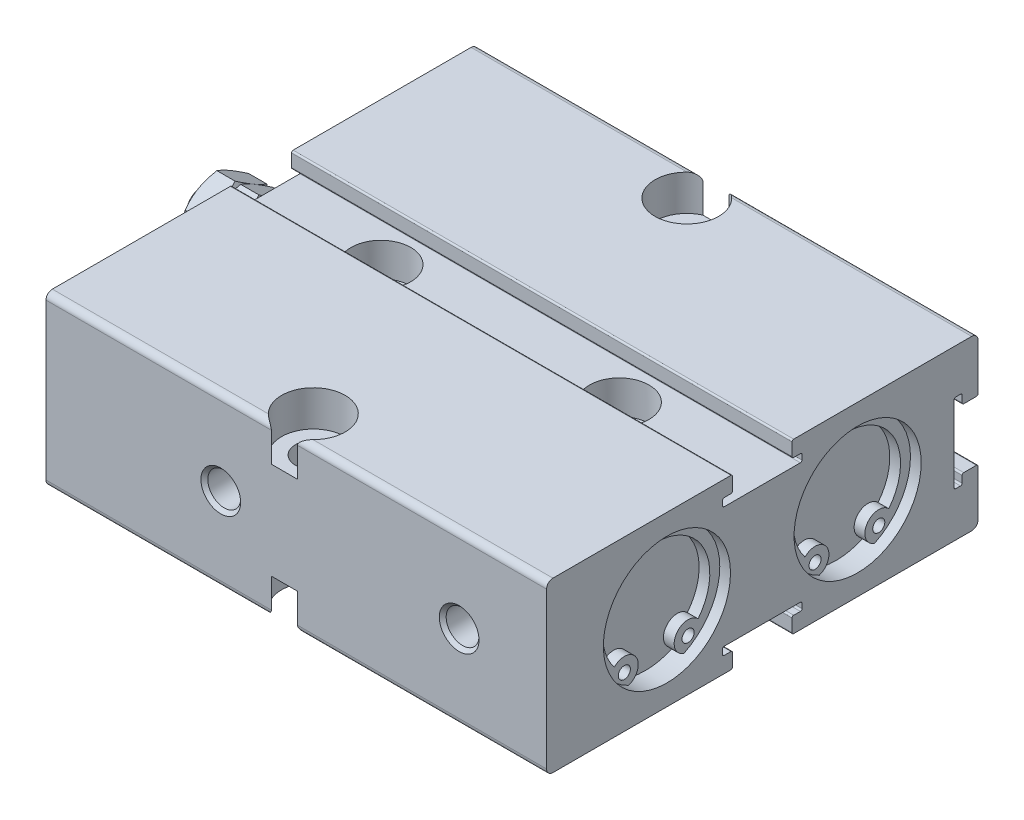
SolidWorks part; units mm, degrees
ref_plane "前视基准面" through (0, 0, 0) normal (0, 0, 1) x (1, 0, 0)
ref_plane "上视基准面" through (0, 0, 0) normal (0, 1, 0) x (1, 0, 0)
ref_plane "右视基准面" through (0, 0, 0) normal (1, 0, 0) x (0, 0, -1)
sketch "草图1" plane through (0, 0, 0) normal (1, 0, 0) x (0, 0, -1)
  line L0 (-26.35, 0) -> (-3.95, 0)
  line L1 (-3.75, 0.2) -> (-3.75, 1.8)
  line L2 (-3.95, 2) -> (-4.8, 2)
  line L3 (-5, 2.2) -> (-5, 2.8)
  line L4 (-4.8, 3) -> (4.8, 3)
  line L5 (5, 2.8) -> (5, 2.2)
  line L6 (4.8, 2) -> (3.95, 2)
  line L7 (3.75, 1.8) -> (3.75, 0.2)
  line L8 (3.95, 0) -> (26.35, 0)
  line L9 (27.15, 0.8) -> (27.15, 6.65)
  line L10 (26.95, 6.85) -> (25.35, 6.85)
  line L11 (25.15, 6.65) -> (25.15, 5.8)
  line L12 (24.95, 5.6) -> (24.35, 5.6)
  line L13 (24.15, 5.8) -> (24.15, 15.4)
  line L14 (24.35, 15.6) -> (24.95, 15.6)
  line L15 (25.15, 15.4) -> (25.15, 14.55)
  line L16 (25.35, 14.35) -> (26.95, 14.35)
  line L17 (27.15, 14.55) -> (27.15, 20.4)
  line L18 (26.35, 21.2) -> (3.95, 21.2)
  line L19 (3.75, 21) -> (3.75, 19.4)
  line L20 (3.95, 19.2) -> (4.8, 19.2)
  line L21 (5, 19) -> (5, 18.4)
  line L22 (4.8, 18.2) -> (-4.8, 18.2)
  line L23 (-5, 18.4) -> (-5, 19)
  line L24 (-4.8, 19.2) -> (-3.95, 19.2)
  line L25 (-3.75, 19.4) -> (-3.75, 21)
  line L26 (-3.95, 21.2) -> (-26.35, 21.2)
  line L27 (-27.15, 20.4) -> (-27.15, 0.8)
  arc A0 (-27.15, 0.8) -> (-26.35, 0) centre (-26.35, 0.8) ccw
  arc A1 (-3.95, 0) -> (-3.75, 0.2) centre (-3.95, 0.2) ccw
  arc A2 (-3.75, 1.8) -> (-3.95, 2) centre (-3.95, 1.8) ccw
  arc A3 (-4.8, 2) -> (-5, 2.2) centre (-4.8, 2.2) cw
  arc A4 (-5, 2.8) -> (-4.8, 3) centre (-4.8, 2.8) cw
  arc A5 (4.8, 3) -> (5, 2.8) centre (4.8, 2.8) cw
  arc A6 (5, 2.2) -> (4.8, 2) centre (4.8, 2.2) cw
  arc A7 (3.95, 2) -> (3.75, 1.8) centre (3.95, 1.8) ccw
  arc A8 (3.75, 0.2) -> (3.95, 0) centre (3.95, 0.2) ccw
  arc A9 (26.35, 0) -> (27.15, 0.8) centre (26.35, 0.8) ccw
  arc A10 (27.15, 6.65) -> (26.95, 6.85) centre (26.95, 6.65) ccw
  arc A11 (25.35, 6.85) -> (25.15, 6.65) centre (25.35, 6.65) ccw
  arc A12 (25.15, 5.8) -> (24.95, 5.6) centre (24.95, 5.8) cw
  arc A13 (24.35, 5.6) -> (24.15, 5.8) centre (24.35, 5.8) cw
  arc A14 (24.15, 15.4) -> (24.35, 15.6) centre (24.35, 15.4) cw
  arc A15 (24.95, 15.6) -> (25.15, 15.4) centre (24.95, 15.4) cw
  arc A16 (25.15, 14.55) -> (25.35, 14.35) centre (25.35, 14.55) ccw
  arc A17 (26.95, 14.35) -> (27.15, 14.55) centre (26.95, 14.55) ccw
  arc A18 (27.15, 20.4) -> (26.35, 21.2) centre (26.35, 20.4) ccw
  arc A19 (3.95, 21.2) -> (3.75, 21) centre (3.95, 21) ccw
  arc A20 (3.75, 19.4) -> (3.95, 19.2) centre (3.95, 19.4) ccw
  arc A21 (4.8, 19.2) -> (5, 19) centre (4.8, 19) cw
  arc A22 (5, 18.4) -> (4.8, 18.2) centre (4.8, 18.4) cw
  arc A23 (-4.8, 18.2) -> (-5, 18.4) centre (-4.8, 18.4) cw
  arc A24 (-5, 19) -> (-4.8, 19.2) centre (-4.8, 19) cw
  arc A25 (-3.95, 19.2) -> (-3.75, 19.4) centre (-3.95, 19.4) ccw
  arc A26 (-3.75, 21) -> (-3.95, 21.2) centre (-3.95, 21) ccw
  arc A27 (-26.35, 21.2) -> (-27.15, 20.4) centre (-26.35, 20.4) ccw
extrude "凸台-拉伸1" add sketch "草图1" along normal blind 63
ref_plane "基准面1" through (0, 0, 12) normal (0, 0, 1) x (1, 0, 0)
sketch "草图2" plane through (0, 0, 12) normal (0, 0, 1) x (1, 0, 0)
  line L0 (0, 10.6) -> (0, 14.6)
  line L1 (0, 14.6) -> (33.4, 14.6)
  line L2 (33.4, 14.6) -> (33.4, 18.6)
  line L3 (33.4, 18.6) -> (57.6, 18.6)
  line L4 (57.6, 18.6) -> (57.6, 10.6)
  line L5 (57.6, 10.6) -> (0, 10.6)
  line L6 (57.6, 10.6) -> (0, 10.6) construction
revolve "切除-旋转1" cut sketch "草图2" angle 360 about L6 reverse direction yes
ref_plane "基准面2" through (0, 0, -12) normal (0, 0, 1) x (1, 0, 0)
sketch "草图3" plane through (0, 0, -12) normal (0, 0, 1) x (1, 0, 0)
  line L0 (0, 10.6) -> (0, 14.6)
  line L1 (0, 14.6) -> (33.4, 14.6)
  line L2 (33.4, 14.6) -> (33.4, 18.6)
  line L3 (33.4, 18.6) -> (57.6, 18.6)
  line L4 (57.6, 18.6) -> (57.6, 10.6)
  line L5 (57.6, 10.6) -> (0, 10.6)
  line L6 (57.6, 10.6) -> (0, 10.6) construction
revolve "切除-旋转2" cut sketch "草图3" angle 360 about L6 reverse direction yes
sketch "草图4" plane through (0, 0, 0) normal (0, 0, 1) x (1, 0, 0)
  line L0 (15, 21.2) -> (18.75, 21.2)
  line L1 (18.75, 21.2) -> (18.75, 14)
  line L2 (18.75, 14) -> (17.25, 14)
  line L3 (17.25, 14) -> (17.25, 7.2)
  line L4 (17.25, 7.2) -> (18.75, 7.2)
  line L5 (18.75, 7.2) -> (18.75, 0)
  line L6 (18.75, 0) -> (15, 0)
  line L7 (15, 0) -> (15, 21.2)
  line L8 (15, 0) -> (15, 21.2) construction
revolve "切除-旋转3" cut sketch "草图4" angle 360 about L8 reverse direction yes
sketch "草图5" plane through (0, 0, 0) normal (0, 0, 1) x (1, 0, 0)
  line L0 (45, 21.2) -> (48.75, 21.2)
  line L1 (48.75, 21.2) -> (48.75, 14)
  line L2 (48.75, 14) -> (47.25, 14)
  line L3 (47.25, 14) -> (47.25, 7.2)
  line L4 (47.25, 7.2) -> (48.75, 7.2)
  line L5 (48.75, 7.2) -> (48.75, 0)
  line L6 (48.75, 0) -> (45, 0)
  line L7 (45, 0) -> (45, 21.2)
  line L8 (45, 0) -> (45, 21.2) construction
revolve "切除-旋转4" cut sketch "草图5" angle 360 about L8 reverse direction yes
ref_plane "基准面3" through (0, 0, 23.5) normal (0, 0, 1) x (1, 0, 0)
sketch "草图6" plane through (0, 0, 23.5) normal (0, 0, 1) x (1, 0, 0)
  line L0 (30, 21.2) -> (34, 21.2)
  line L1 (34, 21.2) -> (34, 16.7)
  line L2 (34, 16.7) -> (32.25, 16.7)
  line L3 (32.25, 16.7) -> (32.25, 4.5)
  line L4 (32.25, 4.5) -> (34, 4.5)
  line L5 (34, 4.5) -> (34, 0)
  line L6 (34, 0) -> (30, 0)
  line L7 (30, 0) -> (30, 21.2)
  line L8 (30, 0) -> (30, 21.2) construction
revolve "切除-旋转5" cut sketch "草图6" angle 360 about L8 reverse direction yes
ref_plane "基准面4" through (0, 0, -23.5) normal (0, 0, 1) x (1, 0, 0)
sketch "草图7" plane through (0, 0, -23.5) normal (0, 0, 1) x (1, 0, 0)
  line L0 (30, 21.2) -> (34, 21.2)
  line L1 (34, 21.2) -> (34, 16.7)
  line L2 (34, 16.7) -> (32.25, 16.7)
  line L3 (32.25, 16.7) -> (32.25, 4.5)
  line L4 (32.25, 4.5) -> (34, 4.5)
  line L5 (34, 4.5) -> (34, 0)
  line L6 (34, 0) -> (30, 0)
  line L7 (30, 0) -> (30, 21.2)
  line L8 (30, 0) -> (30, 21.2) construction
revolve "切除-旋转6" cut sketch "草图7" angle 360 about L8 reverse direction yes
ref_plane "基准面5" through (63, 0, 0) normal (1, 0, 0) x (0, 0, -1)
sketch "草图8" plane through (63, 0, 0) normal (1, 0, 0) x (0, 0, -1)
  circle A0 centre (12, 10.6) radius 8
extrude "切除-拉伸1" cut sketch "草图8" against normal blind 2.7
sketch "草图9" plane through (63, 0, 0) normal (1, 0, 0) x (0, 0, -1)
  circle A0 centre (-12, 10.6) radius 8
extrude "切除-拉伸2" cut sketch "草图9" against normal blind 2.7
sketch "草图10" plane through (0, 0, 0) normal (1, 0, 0) x (0, 0, -1)
  circle A0 centre (12, 10.6) radius 8
extrude "切除-拉伸3" cut sketch "草图10" along normal blind 2.7
sketch "草图11" plane through (0, 0, 0) normal (1, 0, 0) x (0, 0, -1)
  circle A0 centre (-12, 10.6) radius 8
extrude "切除-拉伸4" cut sketch "草图11" along normal blind 2.7
ref_plane "基准面6" through (22, 0, 0) normal (1, 0, 0) x (0, 0, -1)
sketch "草图12" plane through (22, 0, 0) normal (1, 0, 0) x (0, 0, -1)
  line L0 (-27.15, 10.6) -> (-27.15, 13.1)
  line L1 (-27.15, 13.1) -> (-26.717, 12.667)
  line L2 (-26.717, 12.667) -> (-22.15, 12.667)
  line L3 (-22.15, 12.667) -> (-22.15, 10.6)
  line L4 (-22.15, 10.6) -> (-27.15, 10.6)
  line L5 (-22.15, 10.6) -> (-27.15, 10.6) construction
revolve "切除-旋转7" cut sketch "草图12" angle 360 about L5 reverse direction yes
cosmetic thread "装饰螺纹线1" parameters "D1"=5, "D2"=5
ref_plane "基准面7" through (52, 0, 0) normal (1, 0, 0) x (0, 0, -1)
sketch "草图13" plane through (52, 0, 0) normal (1, 0, 0) x (0, 0, -1)
  line L0 (-27.15, 10.6) -> (-27.15, 13.1)
  line L1 (-27.15, 13.1) -> (-26.717, 12.667)
  line L2 (-26.717, 12.667) -> (-22.15, 12.667)
  line L3 (-22.15, 12.667) -> (-22.15, 10.6)
  line L4 (-22.15, 10.6) -> (-27.15, 10.6)
  line L5 (-22.15, 10.6) -> (-27.15, 10.6) construction
revolve "切除-旋转8" cut sketch "草图13" angle 360 about L5 reverse direction yes
cosmetic thread "装饰螺纹线2" parameters "D1"=5, "D2"=5
sketch "草图14" plane through (0, 0, 0) normal (0, 0, 1) x (1, 0, 0)
  line L0 (-6, 13.5) -> (-6, 17.5)
  line L1 (-6, 17.5) -> (-5.5381, 18.3)
  line L2 (-5.5381, 18.3) -> (-3.4619, 18.3)
  line L3 (-3.4619, 18.3) -> (-3, 17.5)
  line L4 (-3, 17.5) -> (-2.5381, 18.3)
  line L5 (-2.5381, 18.3) -> (-0.4619, 18.3)
  line L6 (-0.4619, 18.3) -> (0, 17.5)
  line L7 (0, 17.5) -> (0, 13.5)
  line L8 (0, 13.5) -> (-6, 13.5)
  line L9 (0, 13.5) -> (-6, 13.5) construction
revolve "旋转1" add sketch "草图14" angle 360 about L9 reverse direction yes
sketch "草图15" plane through (0, 0, 0) normal (1, 0, 0) x (0, 0, -1)
  line L0 (-15, -4.4) -> (15, -4.4)
  line L1 (15, -4.4) -> (15, 55.6)
  line L2 (15, 55.6) -> (-15, 55.6)
  line L3 (-15, 55.6) -> (-15, -4.4)
  line L4 (-4, 15.8094) -> (-4, 11.1906)
  line L5 (-4, 11.1906) -> (0, 8.8812)
  line L6 (0, 8.8812) -> (4, 11.1906)
  line L7 (4, 11.1906) -> (4, 15.8094)
  line L8 (4, 15.8094) -> (0, 18.1188)
  line L9 (0, 18.1188) -> (-4, 15.8094)
extrude "切除-拉伸5" cut sketch "草图15" against normal blind 15
sketch "草图16" plane through (0, 0, 0) normal (0, 0, 1) x (1, 0, 0)
  line L0 (-7.5, 13.5) -> (-7.5, 15.5)
  line L1 (-7.5, 15.5) -> (-7, 16)
  line L2 (-7, 16) -> (0, 16)
  line L3 (0, 16) -> (0, 13.5)
  line L4 (0, 13.5) -> (-7.5, 13.5)
  line L5 (0, 13.5) -> (-7.5, 13.5) construction
revolve "旋转2" add sketch "草图16" angle 360 about L5 reverse direction yes
ref_plane "基准面8" through (61.65, 0, 0) normal (1, 0, 0) x (0, 0, -1)
sketch "草图17" plane through (61.65, 0, 0) normal (1, 0, 0) x (0, 0, -1)
  arc A0 (17.0724, 3.6794) -> (6.9276, 3.6794) centre (12, 10.5) ccw
  arc A1 (6.9276, 3.6794) -> (6.729, 6.2834) centre (7.99, 5.07) ccw
  arc A2 (6.729, 6.2834) -> (17.271, 6.2834) centre (12, 10.5) cw
  arc A3 (17.271, 6.2834) -> (17.0724, 3.6794) centre (16.01, 5.07) ccw
  circle A4 centre (16.01, 5.07) radius 0.76
  circle A5 centre (7.99, 5.07) radius 0.76
extrude "凸台-拉伸2" add sketch "草图17" against normal blind 3.75
sketch "草图18" plane through (61.65, 0, 0) normal (1, 0, 0) x (0, 0, -1)
  arc A0 (-6.9276, 3.6794) -> (-17.0724, 3.6794) centre (-12, 10.5) ccw
  arc A1 (-17.0724, 3.6794) -> (-17.271, 6.2834) centre (-16.01, 5.07) ccw
  arc A2 (-17.271, 6.2834) -> (-6.729, 6.2834) centre (-12, 10.5) cw
  arc A3 (-6.729, 6.2834) -> (-6.9276, 3.6794) centre (-7.99, 5.07) ccw
  circle A4 centre (-7.99, 5.07) radius 0.76
  circle A5 centre (-16.01, 5.07) radius 0.76
extrude "凸台-拉伸3" add sketch "草图18" against normal blind 3.75
ref_plane "基准面9" through (1.35, 0, 0) normal (1, 0, 0) x (0, 0, -1)
sketch "草图19" plane through (1.35, 0, 0) normal (1, 0, 0) x (0, 0, -1)
  arc A0 (17.0724, 3.6794) -> (6.9276, 3.6794) centre (12, 10.5) ccw
  arc A1 (6.9276, 3.6794) -> (6.729, 6.2834) centre (7.99, 5.07) ccw
  arc A2 (6.729, 6.2834) -> (17.271, 6.2834) centre (12, 10.5) cw
  arc A3 (17.271, 6.2834) -> (17.0724, 3.6794) centre (16.01, 5.07) ccw
  circle A4 centre (16.01, 5.07) radius 0.76
  circle A5 centre (7.99, 5.07) radius 0.76
extrude "凸台-拉伸4" add sketch "草图19" along normal blind 3.75
sketch "草图20" plane through (1.35, 0, 0) normal (1, 0, 0) x (0, 0, -1)
  arc A0 (-6.9276, 3.6794) -> (-17.0724, 3.6794) centre (-12, 10.5) ccw
  arc A1 (-17.0724, 3.6794) -> (-17.271, 6.2834) centre (-16.01, 5.07) ccw
  arc A2 (-17.271, 6.2834) -> (-6.729, 6.2834) centre (-12, 10.5) cw
  arc A3 (-6.729, 6.2834) -> (-6.9276, 3.6794) centre (-7.99, 5.07) ccw
  circle A4 centre (-7.99, 5.07) radius 0.76
  circle A5 centre (-16.01, 5.07) radius 0.76
extrude "凸台-拉伸5" add sketch "草图20" along normal blind 3.75
ref_plane "基准面10" through (-15, 0, 0) normal (1, 0, 0) x (0, 0, -1)
ref_plane "基准面11" through (1, 0, 0) normal (1, 0, 0) x (0, 0, -1)
ref_plane "基准面12" through (62, 0, 0) normal (1, 0, 0) x (0, 0, -1)
sketch "草图21" plane through (0, 0, 0) normal (0, 0, 1) x (1, 0, 0)
  line L0 (0, 7.7) -> (0, 10.2)
  line L1 (0, 10.2) -> (0.433, 9.767)
  line L2 (0.433, 9.767) -> (5, 9.767)
  line L3 (5, 9.767) -> (5, 7.7)
  line L4 (5, 7.7) -> (0, 7.7)
  line L5 (5, 7.7) -> (0, 7.7) construction
revolve "切除-旋转9" cut sketch "草图21" angle 360 about L5 reverse direction yes
cosmetic thread "装饰螺纹线3" parameters "D1"=5, "D2"=5
ref_plane "for_dummy XY" through (0, 0, 0) normal (1, 0, 0) x (0, 0, -1)
ref_plane "for_dummy XZ" through (0, 0, 0) normal (0, -1, 0) x (-1, 0, 0)
ref_plane "for_dummy YZ" through (0, 0, 0) normal (0, 0, -1) x (-1, 0, 0)
ref_axis "for_dummy X" through (0, 0, 80.9) along (0, 0, -1)
ref_axis "for_dummy Y" through (0, -50, 0) along (0, 1, 0)
ref_axis "for_dummy Z" through (80.9, 0, 0) along (-1, 0, 0)
sketch3d "for_dummy"
  point P0 (0, 0, 0)
ref_plane "for_rod XY" through (-15, 0, 0) normal (-1, 0, 0) x (0, 0, 1)
ref_plane "for_rod XZ" through (0, 10.6, 0) normal (0, 1, 0) x (1, 0, 0)
ref_plane "for_rod YZ" through (0, 0, 0) normal (0, 0, -1) x (-1, 0, 0)
ref_axis "for_rod X" through (-15, 10.6, 80.9) along (0, 0, -1)
ref_axis "for_rod Y" through (-15, 50, 0) along (0, -1, 0)
ref_axis "for_rod Z" through (-80.9, 10.6, 0) along (1, 0, 0)
sketch3d "for_rod"
  point P0 (-15, 10.6, 0)
ref_plane "IP_SWITCH1 XY" through (1, 0, 0) normal (-1, 0, 0) x (0, 0, 1)
ref_plane "IP_SWITCH1 XZ" through (0, 3, 0) normal (0, 1, 0) x (1, 0, 0)
ref_plane "IP_SWITCH1 YZ" through (0, 0, 3.75) normal (0, 0, -1) x (-1, 0, 0)
ref_axis "IP_SWITCH1 X" through (1, 3, 80.9) along (0, 0, -1)
ref_axis "IP_SWITCH1 Y" through (1, 50, 3.75) along (0, -1, 0)
ref_axis "IP_SWITCH1 Z" through (-80.9, 3, 3.75) along (1, 0, 0)
sketch3d "IP_SWITCH1"
  point P0 (1, 3, 3.75)
ref_plane "IP_SWITCH2 XY" through (62, 0, 0) normal (1, 0, 0) x (0, 0, -1)
ref_plane "IP_SWITCH2 XZ" through (0, 14.35, 0) normal (0, -1, 0) x (-1, 0, 0)
ref_plane "IP_SWITCH2 YZ" through (0, 0, -24.15) normal (0, 0, -1) x (-1, 0, 0)
ref_axis "IP_SWITCH2 X" through (62, 14.35, 80.9) along (0, 0, -1)
ref_axis "IP_SWITCH2 Y" through (62, -50, -24.15) along (0, 1, 0)
ref_axis "IP_SWITCH2 Z" through (80.9, 14.35, -24.15) along (-1, 0, 0)
sketch3d "IP_SWITCH2"
  point P0 (62, 14.35, -24.15)
